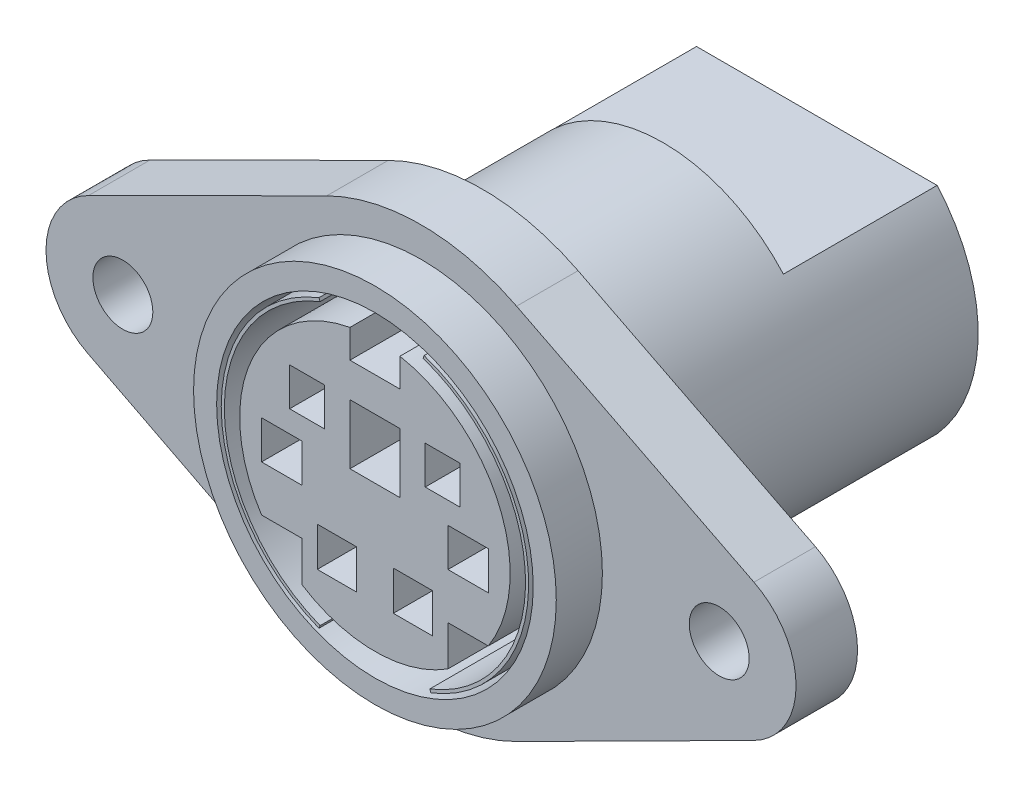
SolidWorks part; units mm, degrees
ref_plane "Plane1" through (0, 0, 0) normal (0, 0, 1) x (1, 0, 0)
ref_plane "Plane2" through (0, 0, 0) normal (0, 1, 0) x (1, 0, 0)
ref_plane "Plane3" through (0, 0, 0) normal (1, 0, 0) x (0, 0, -1)
sketch "Sketch2" plane through (0, 0, 0) normal (0, 0, 1) x (1, 0, 0)
  circle A0 centre (0, 0) radius 5.9944
  dimension "D1" = 11.9888
extrude "Base-Extrude" add sketch "Sketch2" along normal blind 1.524
sketch "Sketch3" plane through (0, 0, 0) normal (0, 0, -1) x (-1, 0, 0)
  line L1 (-3.1583, 6.2302) -> (-11.0037, 2.253)
  line L2 (3.1176, 6.2507) -> (10.9894, 2.3245)
  line L3 (11.0131, -2.2094) -> (3.1828, -6.2177)
  line L4 (-3.1425, -6.2382) -> (-10.998, -2.2809)
  arc A0 (3.1176, 6.2507) -> (-3.1583, 6.2302) centre (0, 0) ccw
  arc A1 (11.0131, -2.2094) -> (10.9894, 2.3245) centre (9.8557, 0.0516) ccw
  arc A2 (-11.0037, 2.253) -> (-10.998, -2.2809) centre (-9.8552, -0.0125) ccw
  arc A3 (-3.1425, -6.2382) -> (3.1828, -6.2177) centre (0, 0) ccw
  dimension "D1" = 13.97
  dimension "D4" = 5.08
  dimension "D5" = 5.08
extrude "Boss-Extrude1" add sketch "Sketch3" along normal blind 2.032
sketch "Sketch4" plane through (0, 0, 0) normal (0, 0, 1) x (1, 0, 0)
  circle A0 centre (9.8552, -0.0125) radius 0.9906
  circle A1 centre (-9.8557, 0.0516) radius 0.9906
  dimension "D1" = 1.9812
extrude "Cut-Extrude1" cut sketch "Sketch4" against normal through all
sketch "Sketch5" plane through (0, 0, -2.032) normal (0, 0, -1) x (-1, 0, 0)
  circle A0 centre (0, 0) radius 5.334
  dimension "D1" = 10.668
extrude "Boss-Extrude2" add sketch "Sketch5" along normal blind 11.049
sketch "Sketch6" plane through (0, 0, -13.081) normal (0, 0, -1) x (-1, 0, 0)
  line L0 (3.9757, 3.556) -> (-3.9757, 3.556)
  line L1 (-3.9757, -3.556) -> (3.9757, -3.556)
  circle A1 centre (0, 0) radius 5.334
  arc A2 (3.9757, 3.556) -> (-3.9757, 3.556) centre (0, 0) ccw
  arc A3 (-3.9757, -3.556) -> (3.9757, -3.556) centre (0, 0) ccw
  dimension "D2" = 3.556
  dimension "D3" = 3.556
  dimension "D1" = 0
extrude "Cut-Extrude2" cut sketch "Sketch6" against normal blind 5.08
sketch "Sketch7" plane through (0, 0, 1.524) normal (0, 0, 1) x (1, 0, 0)
  circle A3 centre (0, 0) radius 5.2324
  circle A4 centre (0, 0) radius 5.2324
  dimension "D2" = 0.762
extrude "Cut-Extrude3" cut sketch "Sketch7" against normal blind 6.35
sketch "Sketch8" plane through (0, 0, -4.826) normal (0, 0, 1) x (1, 0, 0)
  circle A3 centre (0, 0) radius 4.4704
  circle A4 centre (0, 0) radius 4.4704
  dimension "D2" = 0.762
extrude "Boss-Extrude3" add sketch "Sketch8" along normal up to surface (6.35 mm away) up to face at (5.2324, 0, 1.524)
sketch "Sketch10" plane through (0, 0, 1.524) normal (0, 0, 1) x (1, 0, 0)
  line L0 (-0.8255, 4.3935) -> (-0.8255, 3.4544)
  line L1 (0.8255, 4.3935) -> (0.8255, 3.4544)
  line L2 (-0.8255, 2.3245) -> (0.8255, 2.3245)
  line L3 (2.413, -2.4384) -> (2.413, -3.7632)
  line L4 (0.8255, 3.4544) -> (-0.8255, 3.4544)
  line L5 (-0.8255, 2.3245) -> (-0.8255, 0.3472)
  line L6 (-2.413, -2.4384) -> (-2.413, -3.7632)
  line L7 (0.8255, 0.3472) -> (-0.8255, 0.3472)
  line L8 (3.7468, -2.4384) -> (2.413, -2.4384)
  line L9 (-2.413, -2.4384) -> (-3.7468, -2.4384)
  line L10 (0.8255, 0.3472) -> (0.8255, 2.3245)
  line L11 (0, 10.8204) -> (0, -10.287) construction
  line L12 (-1.6621, 2.3245) -> (-2.8194, 2.3245)
  line L13 (-1.6621, 2.3245) -> (-1.6621, 1.0668)
  line L14 (-2.8194, 1.0668) -> (-1.6621, 1.0668)
  line L15 (-2.8194, 1.0668) -> (-2.8194, 2.3245)
  line L16 (1.6621, 2.3245) -> (2.8194, 2.3245)
  line L17 (1.6621, 2.3245) -> (1.6621, 1.0668)
  line L18 (2.8194, 1.0668) -> (1.6621, 1.0668)
  line L19 (2.8194, 1.0668) -> (2.8194, 2.3245)
  line L20 (-2.413, 0.3472) -> (-3.7468, 0.3472)
  line L21 (-2.413, 0.3472) -> (-2.413, -0.9186)
  line L22 (-3.7468, -0.9186) -> (-2.413, -0.9186)
  line L23 (-3.7468, -0.9186) -> (-3.7468, 0.3472)
  line L24 (2.413, 0.3472) -> (3.7468, 0.3472)
  line L25 (2.413, 0.3472) -> (2.413, -0.9186)
  line L26 (3.7468, -0.9186) -> (2.413, -0.9186)
  line L27 (3.7468, -0.9186) -> (3.7468, 0.3472)
  line L28 (-1.905, -1.778) -> (-0.6096, -1.778)
  line L29 (-1.905, -1.778) -> (-1.905, -3.0734)
  line L30 (-0.6096, -3.0734) -> (-1.905, -3.0734)
  line L31 (-0.6096, -3.0734) -> (-0.6096, -1.778)
  line L32 (1.905, -1.778) -> (0.6096, -1.778)
  line L33 (1.905, -1.778) -> (1.905, -3.0734)
  line L34 (0.6096, -3.0734) -> (1.905, -3.0734)
  line L35 (0.6096, -3.0734) -> (0.6096, -1.778)
  circle A1 centre (0, 0) radius 4.4704
  arc A2 (-3.7468, -2.4384) -> (-2.413, -3.7632) centre (0, 0) ccw
  arc A3 (2.413, -3.7632) -> (3.7468, -2.4384) centre (0, 0) ccw
  arc A4 (0.8255, 4.3935) -> (-0.8255, 4.3935) centre (0, 0) ccw
  dimension "D2" = 0.8255
  dimension "D3" = 0.8255
  dimension "D4" = 4.826
  dimension "D5" = 2.413
  dimension "D1" = 0
extrude "Cut-Extrude4" cut sketch "Sketch10" against normal up to surface (6.35 mm away) up to face at (5.2324, 0, -4.826)
sketch "Sketch12" plane through (0, 0, -4.826) normal (0, 0, 1) x (1, 0, 0)
  line L1 (1.592, 4.717) -> (1.6244, 4.8133)
  line L2 (-1.8125, 4.6367) -> (-1.8495, 4.7314)
  line L3 (-1.8125, -4.6367) -> (-1.8495, -4.7314)
  line L4 (1.8125, -4.6367) -> (1.8495, -4.7314)
  arc A0 (-1.8125, 4.6367) -> (-1.8125, -4.6367) centre (0, 0) ccw
  arc A1 (1.8495, -4.7314) -> (1.6244, 4.8133) centre (0, 0) ccw
  arc A2 (-1.8495, 4.7314) -> (-1.8495, -4.7314) centre (0, 0) ccw
  circle A3 centre (0, 0) radius 4.9784
  arc A4 (1.8125, -4.6367) -> (1.592, 4.717) centre (0, 0) ccw
  dimension "D1" = 10.16
  dimension "D3" = 40
  dimension "D2" = 0.254
extrude "Boss-Extrude4" add sketch "Sketch12" along normal up to surface (6.35 mm away) up to face at (5.2324, 0, 1.524)
sketch "Sketch13" plane through (0, 0, -13.081) normal (0, 0, -1) x (-1, 0, 0)
  point P0 (0, 0)
other "CPoint1"
ref_axis "Axis1" through (0, 0, -23.081) along (0, 0, 1)
